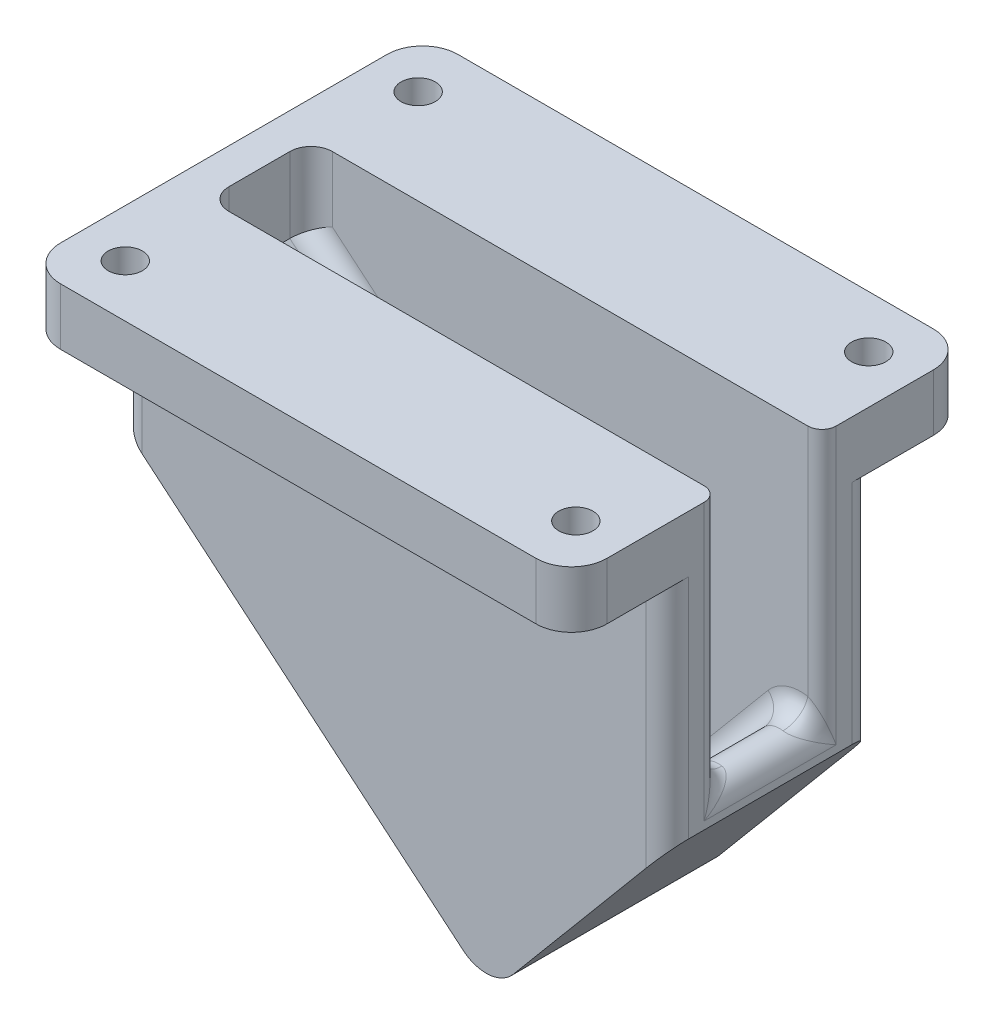
SolidWorks part; units mm, degrees
ref_plane "Front Plane" through (0, 0, 0) normal (0, 0, 1) x (1, 0, 0)
ref_plane "Top Plane" through (0, 0, 0) normal (0, 1, 0) x (1, 0, 0)
ref_plane "Right Plane" through (0, 0, 0) normal (1, 0, 0) x (0, 0, -1)
sketch "Sketch2" plane through (0, 0, 0) normal (0, 0, 1) x (1, 0, 0)
  line L0 (-38.5, 0) -> (38.5, 0)
  line L3 (-38.5, 0) -> (-38.5, -26)
  line L4 (-38.5, -26) -> (13.5791, -69.6996)
  line L5 (13.5791, -69.6996) -> (38.5, -40)
  line L6 (38.5, -40) -> (38.5, 0)
  line L7 (-20.4377, -21.575) -> (-30.0795, -33.0657) construction
  line L8 (-33.5, -10.6144) -> (18.6247, -54.3522)
  line L9 (18.6247, -54.3522) -> (38.5, -30.6657)
  line L10 (10.2041, -47.2865) -> (0.5623, -58.7772) construction
  line L11 (-33.5, -10.6144) -> (-33.5, 0)
  line L12 (-20.4377, -21.575) -> (0.5623, -58.7772) construction
  line L14 (-38.5, -26) -> (18.6247, -54.3522) construction
  point P10 (-5.8493, -42.6067)
  point P13 (-9.9377, -40.1761)
  dimension "D1" = 40
  dimension "D2" = 26
  dimension "D3" = 15
  dimension "D4" = 77
  dimension "D5" = 6
  dimension "D6" = 40
  dimension "D7" = 5
  dimension "D9" = 40
extrude "Boss-Extrude1" add sketch "Sketch2" along normal mid plane 29 contours L8 L11 L0 L3 L4 L5 L6 L9 | L11 L8 L9 L6 L0 region at (-5.8897, -39.4379, 0) region at (8.1407, -19.7304, 0)
extrude "Cut-Extrude1" cut sketch "Sketch2<4>" against normal mid plane 14.6 contours L11 L8 L9 L6 L0 region at (8.1407, -19.7304, 0)
sketch "Sketch2<4>" plane through (0, 0, 0) normal (0, 0, 1) x (1, 0, 0) same geometry as "Sketch2"
sketch "Sketch3" plane through (0, 0, 0) normal (0, 1, 0) x (1, 0, 0)
  line L0 (38.5, -14.5) -> (38.5, -7.3) construction
  line L1 (-38.5, 28) -> (38.5, 28)
  line L2 (-38.5, 28) -> (-38.5, -28)
  line L3 (-38.5, -28) -> (38.5, -28)
  line L4 (38.5, 28) -> (38.5, -28)
  line L5 (-38.5, -14.5) -> (-38.5, 14.5) construction
  line L6 (-31.75, 20.6375) -> (31.75, -20.6375) construction
  line L7 (-31.75, 20.6375) -> (31.75, 20.6375) construction
  line L8 (-31.75, 20.6375) -> (-31.75, -20.6375) construction
  line L9 (-31.75, -20.6375) -> (31.75, -20.6375) construction
  line L10 (31.75, 20.6375) -> (31.75, -20.6375) construction
  line L11 (-38.5, 14.5) -> (38.5, 14.5) construction
  line L12 (-38.5, 14.5) -> (38.5, 14.5)
  line L13 (-38.5, -14.5) -> (38.5, -14.5) construction
  line L14 (-38.5, -14.5) -> (38.5, -14.5)
  circle A0 centre (-31.75, 20.6375) radius 2.413
  circle A1 centre (-31.75, -20.6375) radius 2.413
  circle A2 centre (31.75, 20.6375) radius 2.413
  circle A3 centre (31.75, -20.6375) radius 2.413
  point P9 (-38.5, 0)
  line M8 (38.5, 14.5) -> (-38.5, 14.5)
  line M10 (-38.5, -14.5) -> (38.5, -14.5)
  dimension "D2" = 4.826
  dimension "D1" = 56
  dimension "D3" = 41.275
  dimension "D4" = 63.5
extrude "Boss-Extrude2" add sketch "Sketch3" against normal blind 8 contours L4 L1 L2 A2 A0 M8 | L4 L2 L3 A3 A1 M10 region at (0, 0, -21.2723) region at (0, 0, 21.2723)
sketch "Sketch4" plane through (-19.068, -22.7243, 0) normal (0.6428, 0.766, 0) x (0.766, -0.6428, 0)
  line L0 (-1.788, 0) -> (38.212, 0) construction
  line L3 (2.4266, -7.3) -> (6.6413, 0)
  line L4 (6.6413, 0) -> (2.4266, 7.3)
  line L5 (2.4266, 7.3) -> (-6.0027, 7.3)
  line L6 (-6.0027, 7.3) -> (-10.2173, 0)
  line L7 (-10.2173, 0) -> (-6.0027, -7.3)
  line L8 (-6.0027, -7.3) -> (2.4266, -7.3)
  line L9 (46.6413, 0) -> (42.4266, 7.3)
  line L10 (42.4266, 7.3) -> (33.9973, 7.3)
  line L11 (33.9973, 7.3) -> (29.7827, 0)
  line L12 (29.7827, 0) -> (33.9973, -7.3)
  line L13 (33.9973, -7.3) -> (42.4266, -7.3)
  line L14 (42.4266, -7.3) -> (46.6413, 0)
  circle A0 centre (-1.788, 0) radius 4.8
  circle A1 centre (38.212, 0) radius 4.8
  circle A2 centre (-1.788, 0) radius 7.3 construction
  circle A3 centre (38.212, 0) radius 7.3 construction
  point P5 (0, 0)
  point P6 (0, 0)
  point P10 (-3.675, 0)
  dimension "D2" = 9.6
  dimension "D1" = 40
  dimension "D3" = 14.6
extrude "Cut-Extrude2" cut sketch "Sketch4" against normal blind 6.35
extrude "Cut-Extrude3" cut sketch "Sketch4<2>" against normal through all contours A0 | A1
sketch "Sketch4<2>" plane through (-19.068, -22.7243, 0) normal (0.6428, 0.766, 0) x (0.766, -0.6428, 0) same geometry as "Sketch4"
fillet "Fillet1" radius 3 2 edges at (38.5, -30.6657, 0) (18.6247, -54.3522, 0)
fillet "Fillet2" radius 5 4 edges at (-38.5, -4, 28) (-38.5, -4, -28) (38.5, -4, -28) (38.5, -4, 28)
fillet "Fillet3" radius 5 1 edges at (13.5791, -69.6996, 0)
fillet "Fillet5" radius 2 2 edges at (38.5, -19.454, -7.3) (38.5, -19.454, 7.3)
fillet "Fillet6" radius 3 16 edges at (14.8796, -51.2097, 7.3) (18.5164, -53.1143, 7.3) (37.7403, -36.9128, 7.731) (34.7102, -36.0139, 7.3) (37.7403, -36.9128, -7.731) (34.7102, -36.0139, -7.3) (26.8774, -44.5169, -7.3) (18.5164, -53.1143, -7.3) (-33.5, -5.3072, 7.3) (-33.5, -5.3072, -7.3) (-28.5831, -14.7401, -7.3) (-28.5831, -14.7401, 7.3) (-5.1168, -34.4308, 7.3) (26.8774, -44.5169, 7.3) (-5.1168, -34.4308, -7.3) (14.8796, -51.2097, -7.3)
fillet "Fillet7" radius 3 4 edges at (38.5, -24, 14.5) (38.5, -24, -14.5) (-38.5, -17, 14.5) (-38.5, -17, -14.5)
